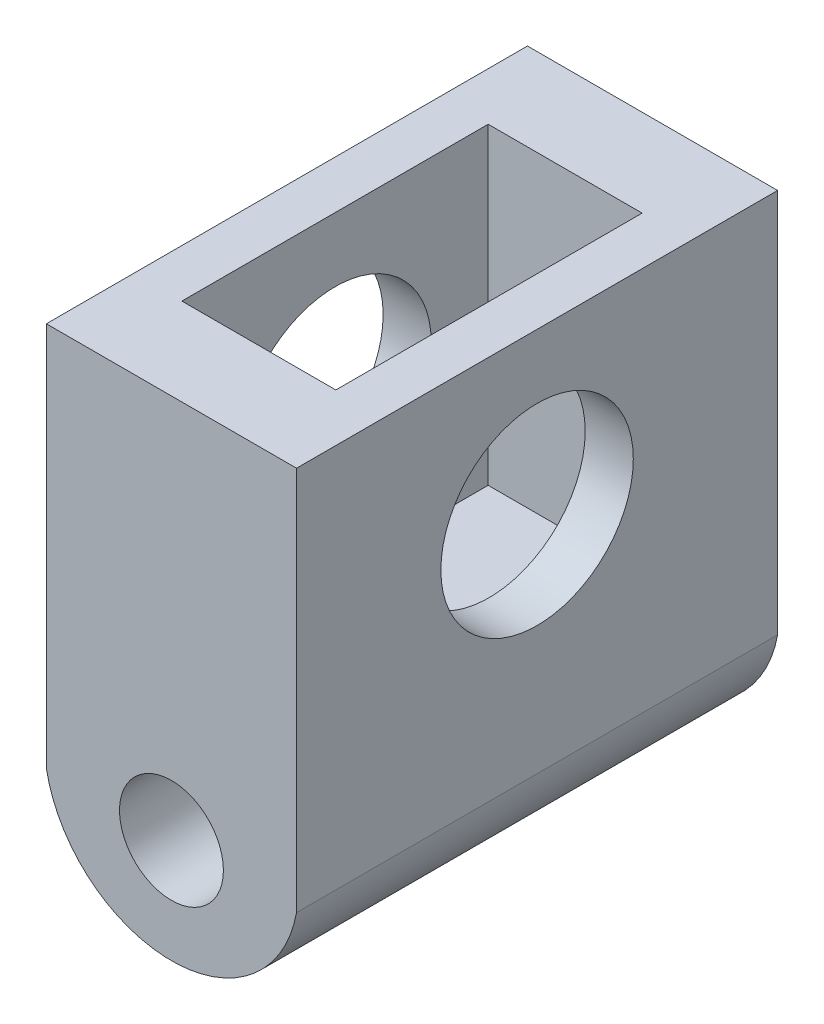
SolidWorks part; units mm, degrees
material "PBT General Purpose"
ref_plane "Front" through (0, 0, 0) normal (0, 0, 1) x (1, 0, 0)
ref_plane "Top" through (0, 0, 0) normal (0, 1, 0) x (1, 0, 0)
ref_plane "Right" through (0, 0, 0) normal (1, 0, 0) x (0, 0, -1)
sketch "Sketch1" plane through (0, 0, 0) normal (0, 0, 1) x (1, 0, 0)
  line L1 (-7.8, 0) -> (-7.8, 24)
  line L2 (7.8, 0) -> (7.8, 24)
  line L3 (-7.8, 24) -> (7.8, 24)
  circle A0 centre (0, 0) radius 3.2385
  arc A2 (7.8, 0) -> (-7.8, 0) centre (0, 1.43) cw
  point P5 (0, 24)
  point P7 (0, -6.5)
  dimension "D1" = 6.477
  dimension "D2" = 15.6
  dimension "D3" = 24
  dimension "D4" = 6.5
extrude "Boss-Extrude1" add sketch "Sketch1" along normal blind 15 and the other way blind 15
sketch "Sketch2" plane through (-7.8, 0, 0) normal (-1, 0, 0) x (0, 0, 1)
  line L0 (-15, 24) -> (15, 24) construction
  line L1 (-9.55, 24) -> (9.55, 24)
  line L2 (-9.55, 24) -> (-9.55, 4.5)
  line L3 (-9.55, 4.5) -> (9.55, 4.5)
  line L4 (9.55, 24) -> (9.55, 4.5)
  line L5 (-15, 0) -> (15, 0) construction
  point P6 (0, 24)
  point P9 (0, 0)
  dimension "D1" = 19.1
  dimension "D2" = 19.5
extrude "Cut-Extrude1" cut sketch "Sketch2" against normal offset from surface (9.6 mm away) 3 from offset 3 up to face at (7.8, 12, 0) offset against normal yes
sketch "Sketch3" plane through (-7.8, 0, 0) normal (-1, 0, 0) x (0, 0, 1)
  line L0 (-15, 24) -> (15, 24) construction
  line L1 (-9.55, 4.5) -> (9.55, 4.5) construction
  line L2 (-15, 0) -> (15, 0) construction
  circle A0 centre (0, 14) radius 6
  point P6 (0, 0)
  point P9 (0, 0)
  dimension "D1" = 12
  dimension "D2" = 10
  dimension "D3" = 9.5
extrude "Cut-Extrude2" cut sketch "Sketch3" against normal through all both and the other way through all
